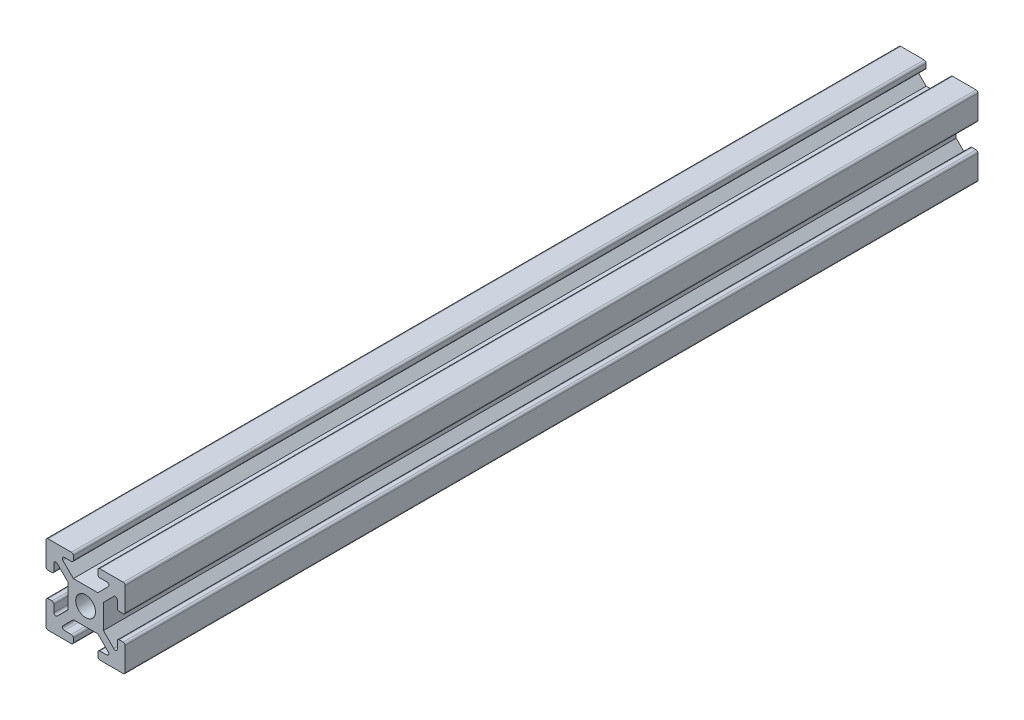
SolidWorks part; units mm, degrees
material "3.2381 (EN-AW-43000)"
ref_plane "Ebene vorne" through (0, 0, 0) normal (0, 0, 1) x (1, 0, 0)
ref_plane "Ebene oben" through (0, 0, 0) normal (0, 1, 0) x (1, 0, 0)
ref_plane "Ebene rechts" through (0, 0, 0) normal (1, 0, 0) x (0, 0, -1)
sketch "Skizze1" plane through (0, 0, 0) normal (0, 0, 1) x (1, 0, 0)
  line L0 (-0.7071, 0.7071) -> (6.5858, 8)
  line L1 (-10, -10) -> (10, -10) construction
  line L2 (-10, -10) -> (-10, 10) construction
  line L3 (-10, 10) -> (10, 10) construction
  line L4 (10, -10) -> (10, 10) construction
  line L5 (-10, -10) -> (10, 10) construction
  line L6 (-10, 10) -> (10, -10) construction
  line L7 (6.5858, 8) -> (3.1, 8)
  line L8 (3.1, 8) -> (3.1, 10)
  line L9 (3.1, 10) -> (10, 10)
  line L10 (10, 10) -> (10, 3.1)
  line L11 (10, 3.1) -> (8, 3.1)
  line L12 (8, 3.1) -> (8, 6.5858)
  line L13 (8, 6.5858) -> (0.7071, -0.7071)
  line L14 (0.7071, -0.7071) -> (-0.7071, 0.7071)
  point P0 (0, 0)
  point P14 (0, 0)
  dimension "D1" = 2
  dimension "D2" = 3.1
  dimension "D3" = 20
extrude "Aufsatz-Linear austragen1" add sketch "Skizze1" along normal blind 215.4
sketch "Skizze2" plane through (0, 0, 0) normal (-0.7071, -0.7071, 0) x (0, 0, 1)
  line L0 (0, 0) -> (215.4, 0) construction
  line L1 (215.4, 1) -> (215.4, -1) construction
fillet "Verrundung1" radius 0.5 7 edges at (6.5858, 8, 107.7) (8, 6.5858, 107.7) (10, 10, 107.7) (3.1, 8, 107.7) (8, 3.1, 107.7) (10, 3.1, 107.7) (3.1, 10, 107.7)
pattern_circular "Kreismuster1" count 4 over 360 about axis through (0, 0, 0) along (0, 0, 1) of "Aufsatz-Linear austragen1", "Verrundung1"
sketch "Skizze3" plane through (0, 0, 215.4) normal (0, 0, 1) x (1, 0, 0)
  line L1 (-4.5, -4.5) -> (4.5, -4.5)
  line L2 (-4.5, -4.5) -> (-4.5, 4.5)
  line L3 (-4.5, 4.5) -> (4.5, 4.5)
  line L4 (4.5, -4.5) -> (4.5, 4.5)
  line L5 (-4.5, -4.5) -> (4.5, 4.5) construction
  line L6 (-4.5, 4.5) -> (4.5, -4.5) construction
  point P0 (0, 0)
  dimension "D1" = 9
extrude "Aufsatz-Linear austragen2" add sketch "Skizze3" against normal up to surface (215.4 mm away) up to face at (0, 0, 0)
sketch "Skizze4" plane through (0, 0, 215.4) normal (0, 0, 1) x (1, 0, 0)
  circle A0 centre (0, 0) radius 2.5
  dimension "D1" = 5
extrude "Schnitt-Linear austragen1" cut sketch "Skizze4" against normal through all
equation "\"Plungerplate_Width\"= 160"
equation "\"D1@Aufsatz-Linear austragen1\"=\"Plungerplate_Width\""
